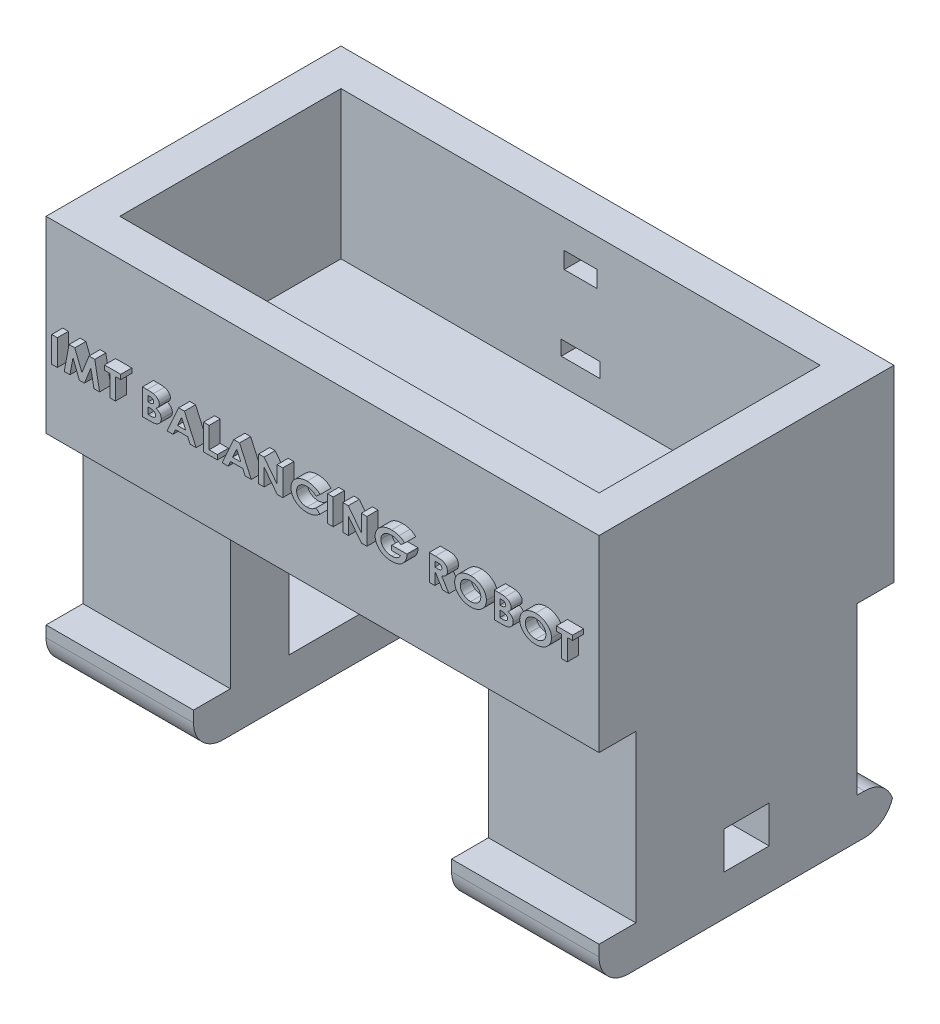
SolidWorks part; units mm, degrees
ref_plane "Alzado" through (0, 0, 0) normal (0, 0, 1) x (1, 0, 0)
ref_plane "Planta" through (0, 0, 0) normal (0, 1, 0) x (1, 0, 0)
ref_plane "Vista lateral" through (0, 0, 0) normal (1, 0, 0) x (0, 0, -1)
sketch "Croquis1" plane through (0, 0, 0) normal (0, 1, 0) x (1, 0, 0)
  line L0 (0, 40) -> (0, -40) construction
  line L1 (75, -40) -> (-75, -40)
  line L2 (75, -40) -> (75, 40)
  line L3 (75, 40) -> (-75, 40)
  line L4 (-75, -40) -> (-75, 40)
  line L5 (75, -40) -> (-75, 40) construction
  line L6 (75, 40) -> (-75, -40) construction
  line L7 (-75, 0) -> (75, 0) construction
  point P0 (0, 0)
  dimension "D1" = 150
  dimension "D2" = 80
extrude "Saliente-Extruir1" add sketch "Croquis1" along normal blind 2
sketch "Croquis2" plane through (0, 2, 0) normal (0, 1, 0) x (1, 0, 0)
  line L0 (-75, -40) -> (75, -40) construction
  line L1 (-75, 40) -> (-35, 40)
  line L2 (-75, 40) -> (-75, -40)
  line L3 (-75, -40) -> (-35, -40)
  line L4 (-35, 40) -> (-35, -40)
  dimension "D1" = 40
extrude "Saliente-Extruir2" add sketch "Croquis2" along normal blind 65
ref_plane "Plano1" through (0, 0, 0) normal (1, 0, 0) x (0, 0, -1)
sketch "Croquis3" plane through (-75, 0, 0) normal (-1, 0, 0) x (0, 0, 1)
  line L0 (0, 67) -> (0, 0) construction
  line L1 (-40, 67) -> (40, 67) construction
  line L2 (-40, 33.5) -> (40, 33.5) construction
  line L3 (-40, 67) -> (-40, 0) construction
  line L4 (40, 67) -> (40, 0) construction
  line L5 (30, 56) -> (40, 56)
  line L6 (30, 11) -> (30, 56)
  line L7 (30, 11) -> (40, 11)
  point P18 (30, 33.5)
  dimension "D1" = 10
  dimension "D2" = 45
extrude "Cortar-Extruir1" cut sketch "Croquis3" against normal through all and the other way through all
ref_plane "Plano2" through (0, 0, 0) normal (0, 0, 1) x (1, 0, 0)
mirror "Simetría1" about plane through (0, 0, 0) normal (0, 0, 1) of "Cortar-Extruir1"
mirror "Simetría2" about plane through (0, 0, 0) normal (1, 0, 0) of "Saliente-Extruir2", "Simetría1", "Cortar-Extruir1"
sketch "Croquis4" plane through (0, 2, 0) normal (0, 1, 0) x (1, 0, 0)
  line L1 (-35, 40) -> (35, 40)
  line L2 (-35, 40) -> (-35, -40)
  line L3 (-35, -40) -> (35, -40)
  line L4 (35, 40) -> (35, -40)
extrude "Cortar-Extruir2" cut sketch "Croquis4" against normal through all
sketch "Croquis5" plane through (0, 67, 0) normal (0, 1, 0) x (1, 0, 0)
  line L1 (-35, 40) -> (35, 40)
  line L2 (-35, 40) -> (-35, -40)
  line L3 (-35, -40) -> (35, -40)
  line L4 (35, 40) -> (35, -40)
extrude "Saliente-Extruir3" add sketch "Croquis5" against normal up to surface (11 mm away) up to face at (55, 56, 35)
sketch "Croquis6" plane through (75, 0, 0) normal (1, 0, 0) x (0, 0, -1)
  line L0 (30, 11) -> (40, 11) construction
  line L5 (0, 67) -> (0, 0) construction
  line L6 (40, 67) -> (-40, 67) construction
  line L7 (6.15, 11) -> (-6.15, 11)
  line L8 (6.15, 11) -> (6.15, 21.1)
  line L9 (6.15, 21.1) -> (-6.15, 21.1)
  line L10 (-6.15, 11) -> (-6.15, 21.1)
  line L11 (6.15, 11) -> (-6.15, 21.1) construction
  line L12 (6.15, 21.1) -> (-6.15, 11) construction
  point P4 (0, 16.05)
  dimension "D1" = 10.1
  dimension "D2" = 12.3
extrude "Cortar-Extruir3" cut sketch "Croquis6" against normal through all
fillet "Redondeo1" radius 8 10 edges at (-55, 0, -40) (-55, 11, -40) (-55, 0, 40) (-75, 5.5, -40) (35, 5.5, -40) (55, 11, -40) (55, 0, 40) (55, 0, -40) (75, 5.5, -40) (-35, 5.5, -40)
sketch "Croquis8" plane through (0, 67, 0) normal (0, 1, 0) x (1, 0, 0)
  line L0 (-75, -40) -> (-75, 40) construction
  line L1 (-65, -30) -> (65, -30)
  line L2 (-65, -30) -> (-65, 30)
  line L3 (-65, 30) -> (65, 30)
  line L4 (65, -30) -> (65, 30)
  line L5 (-65, -30) -> (65, 30) construction
  line L6 (-65, 30) -> (65, -30) construction
  line L7 (75, 40) -> (-75, 40) construction
  point P0 (0, 0)
  line M3 (-75, 40) -> (-75, -40)
  line M4 (-75, -40) -> (75, -40)
  line M5 (75, -40) -> (75, 40)
  line M6 (75, 40) -> (-75, 40)
  dimension "D1" = 10
  dimension "D2" = 10
extrude "Saliente-Extruir5" add sketch "Croquis8" along normal blind 40 contours L4 L1 L2 L3 M6 M3 M4 M5
sketch "Croquis10" plane through (0, 67, 0) normal (0, 1, 0) x (1, 0, 0)
  text T0 "<b>BATERIA</b>" font "Century Gothic" height in points 36
extrude "Cortar-Extruir5" cut sketch "Croquis10" against normal blind 5
sketch "Croquis11" plane through (0, 0, -40) normal (0, 0, -1) x (-1, 0, 0)
  line L0 (0, 56) -> (0, 107) construction
  line L1 (75, 56) -> (-75, 56) construction
  line L2 (-75, 107) -> (75, 107) construction
  line L4 (5.25, 74) -> (-5.25, 74)
  line L5 (5.25, 74) -> (5.25, 78)
  line L6 (5.25, 78) -> (-5.25, 78)
  line L7 (-5.25, 74) -> (-5.25, 78)
  line L8 (5.25, 74) -> (-5.25, 78) construction
  line L9 (5.25, 78) -> (-5.25, 74) construction
  line L10 (-4.45, 99.25) -> (4.45, 99.25)
  line L11 (-4.45, 99.25) -> (-4.45, 94.75)
  line L12 (-4.45, 94.75) -> (4.45, 94.75)
  line L13 (4.45, 99.25) -> (4.45, 94.75)
  line L14 (-4.45, 99.25) -> (4.45, 94.75) construction
  line L15 (-4.45, 94.75) -> (4.45, 99.25) construction
  point P6 (0, 76)
  point P11 (0, 97)
  dimension "D1" = 20
  dimension "D2" = 4
  dimension "D3" = 10.5
  dimension "D4" = 8.9
  dimension "D5" = 4.5
  dimension "D6" = 10
extrude "Cortar-Extruir6" cut sketch "Croquis11" against normal up to next
sketch "Croquis12" plane through (0, 0, 40) normal (0, 0, 1) x (1, 0, 0)
  line L0 (-75, 76) -> (75, 76) construction
  line L3 (-75, 56) -> (75, 56) construction
  text T0 "<b>IMT BALANCING ROBOT</b>" font "Century Gothic" height 7
  dimension "D1" = 20
extrude "Saliente-Extruir8" add sketch "Croquis12" along normal blind 3
sketch "Croquis13" plane through (35, 0, 0) normal (-1, 0, 0) x (0, 0, 1)
  line L1 (14.15, 11) -> (-14.15, 11)
  line L2 (14.15, 11) -> (14.15, 56)
  line L3 (14.15, 56) -> (-14.15, 56)
  line L4 (-14.15, 11) -> (-14.15, 56)
  line L6 (-6.15, 11) -> (6.15, 11) construction
  line L7 (-30, 56) -> (30, 56) construction
  line L8 (6.15, 11) -> (6.15, 21.1) construction
  point P4 (0, 0)
  point P5 (12.5051, 56)
  point P6 (0, 11)
  dimension "D1" = 8
extrude "Cortar-Extruir7" cut sketch "Croquis13" against normal blind 20
sketch "Croquis14" plane through (0, 56, 0) normal (0, -1, 0) x (1, 0, 0)
  line L0 (200153.7667, 0) -> (-200153.6095, 0) construction
  line L1 (55, -5) -> (45, -5)
  line L2 (55, -5) -> (55, 5)
  line L3 (55, 5) -> (45, 5)
  line L4 (45, -5) -> (45, 5)
  line L5 (55, -5) -> (45, 5) construction
  line L6 (55, 5) -> (45, -5) construction
  line L8 (55, 14.15) -> (55, -14.15) construction
  point P0 (50, 0)
  point P7 (63, -5.9341)
  dimension "D1" = 10
  dimension "D2" = 10
extrude "Cortar-Extruir8" cut sketch "Croquis14" against normal through all
mirror "Simetría3" about plane through (0, 0, 0) normal (1, 0, 0) of "Cortar-Extruir8", "Cortar-Extruir7"
